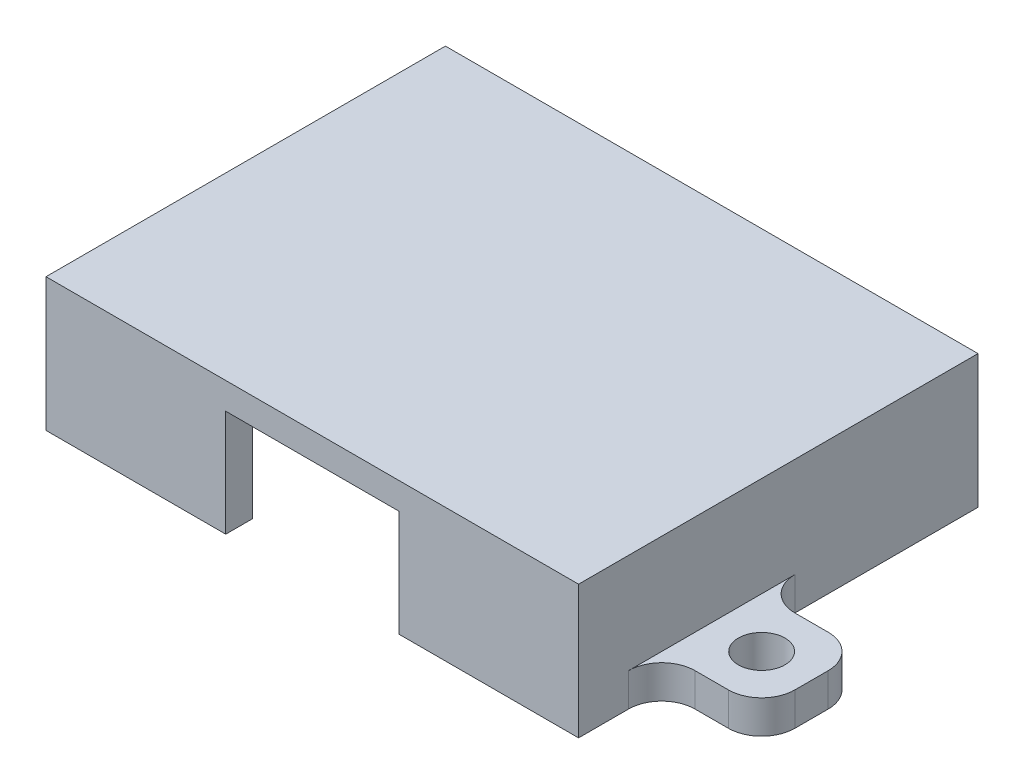
SolidWorks part; units mm, degrees
ref_plane "Front Plane" through (0, 0, 0) normal (0, 0, 1) x (1, 0, 0)
ref_plane "Top Plane" through (0, 0, 0) normal (0, 1, 0) x (1, 0, 0)
ref_plane "Right Plane" through (0, 0, 0) normal (1, 0, 0) x (0, 0, -1)
sketch "Sketch1" plane through (0, 0, 0) normal (0, 1, 0) x (1, 0, 0)
  line L1 (0, 0) -> (40, 0)
  line L2 (0, 0) -> (0, 30)
  line L3 (0, 30) -> (40, 30)
  line L4 (40, 0) -> (40, 30)
  dimension "D1" = 40
  dimension "D2" = 30
extrude "Boss-Extrude1" add sketch "Sketch1" along normal blind 10
sketch "Sketch2" plane through (0, 0, 0) normal (0, -1, 0) x (1, 0, 0)
  line L0 (13.5, 0) -> (26.5, 0)
  line L1 (0, 0) -> (40, 0) construction
  line L2 (26.5, 0) -> (26.5, -2)
  line L3 (26.5, -2) -> (38, -2)
  line L4 (38, -2) -> (38, -28)
  line L6 (2, -28) -> (2, -2)
  line L7 (2, -2) -> (13.5, -2)
  line L8 (13.5, -2) -> (13.5, 0)
  line L9 (40, 0) -> (40, -30) construction
  line L10 (0, -30) -> (0, 0) construction
  line L11 (40, -30) -> (0, -30) construction
  line L12 (2, -28) -> (2, -30)
  line L13 (2, -30) -> (8, -30)
  line L14 (8, -30) -> (8, -28)
  line L15 (8, -28) -> (32, -28)
  line L16 (32, -28) -> (32, -30)
  line L17 (32, -30) -> (38, -30)
  line L18 (38, -30) -> (38, -28)
  point P16 (20, 0)
  point P17 (20, -30)
  dimension "D1" = 13
  dimension "D2" = 2
  dimension "D3" = 2
  dimension "D4" = 2
  dimension "D5" = 2
  dimension "D6" = 6
extrude "Cut-Extrude1" cut sketch "Sketch2" against normal offset from surface (8 mm away) 2 up to face at (20, 10, -15)
sketch "Sketch3" plane through (0, 0, 0) normal (-1, 0, 0) x (0, 0, 1)
  line L0 (-30, 0) -> (0, 0) construction
  line L1 (-6.25, 0) -> (-13.75, 0)
  line L2 (-6.25, 0) -> (-6.25, 2.5)
  line L3 (-6.25, 2.5) -> (-13.75, 2.5)
  line L4 (-13.75, 0) -> (-13.75, 2.5)
  line L5 (0, 10) -> (0, 0) construction
  point P6 (-10, 2.5)
  dimension "D1" = 7.5
  dimension "D2" = 10
  dimension "D3" = 2.5
extrude "Boss-Extrude2" add sketch "Sketch3" along normal blind 7.5
sketch "Sketch4" plane through (0, 2.5, 0) normal (0, 1, 0) x (1, 0, 0)
  line L0 (-7.5, 13.75) -> (0, 13.75) construction
  line L1 (-7.5, 6.25) -> (-7.5, 13.75) construction
  circle A0 centre (-3.75, 10) radius 1.75
  point P2 (-3.75, 13.75)
  point P3 (-7.5, 10)
  point P6 (0, 0)
  point P9 (0, 0)
  dimension "D1" = 3.5
extrude "Cut-Extrude2" cut sketch "Sketch4" against normal through all
fillet "Fillet1" radius 2.5 4 edges at (0, 1.25, -6.25) (-7.5, 1.25, -6.25) (-7.5, 1.25, -13.75) (0, 1.25, -13.75)
ref_plane "Plane1" through (20, 0, 0) normal (-1, 0, 0) x (0, 0, 1)
mirror "Mirror1" about plane through (20, 0, 0) normal (-1, 0, 0) of "Boss-Extrude2", "Cut-Extrude2"
fillet "Fillet2" radius 2.5 4 edges at (47.5, 1.25, -13.75) (40, 1.25, -13.75) (47.5, 1.25, -6.25) (40, 1.25, -6.25)
